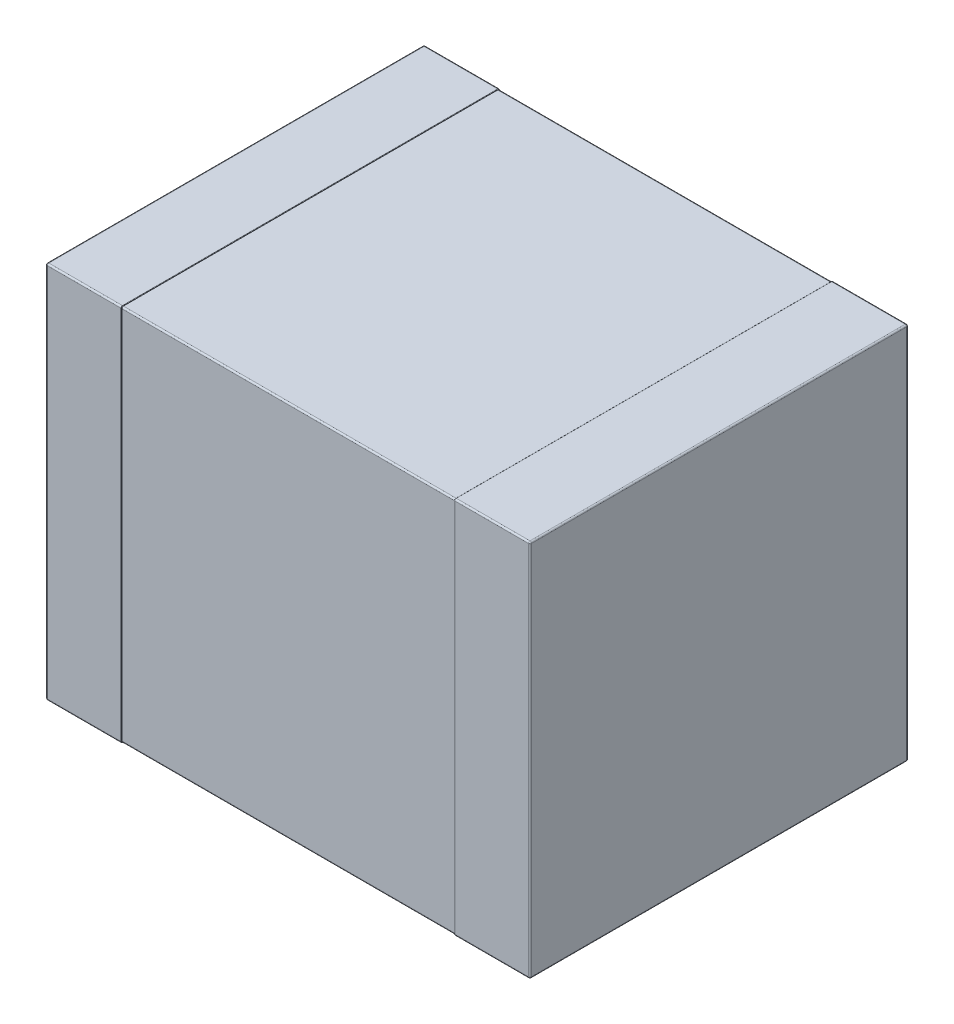
SolidWorks part; units mm, degrees
ref_plane "Top Plane" through (0, 0, 0) normal (0, 0, 1) x (1, 0, 0)
ref_plane "Front Plane" through (0, 0, 0) normal (0, 1, 0) x (1, 0, 0)
ref_plane "Side Plane" through (0, 0, 0) normal (1, 0, 0) x (0, 0, -1)
sketch "Sketch1" plane through (0, 0, 0) normal (0, 0, 1) x (1, 0, 0)
  line L1 (-1.6, 1.25) -> (1.6, 1.25)
  line L2 (-1.6, 1.25) -> (-1.6, -1.25)
  line L3 (-1.6, -1.25) -> (1.6, -1.25)
  line L4 (1.6, 1.25) -> (1.6, -1.25)
  dimension "D1" = 3.2
  dimension "D2" = 1.6
  dimension "D3" = 2.5
  dimension "D4" = 1.25
extrude "All body" add sketch "Sketch1" along normal blind 2.5
sketch "Sketch2" plane through (0, 0, 0) normal (1, 0, 0) x (0, 0, -1)
  line L14 (-0.003, 1.247) -> (-2.497, 1.247)
  line L15 (-0.003, -1.247) -> (-0.003, 1.247)
  line L16 (-2.497, -1.247) -> (-0.003, -1.247)
  line L17 (-2.497, 1.247) -> (-2.497, -1.247)
  line L18 (-0.003, 1.247) -> (-2.497, 1.247)
  line L19 (-0.003, -1.247) -> (-0.003, 1.247)
  line L20 (-2.497, -1.247) -> (-0.003, -1.247)
  line L21 (-2.497, 1.247) -> (-2.497, -1.247)
  dimension "D1" = 0.003
extrude "Cut out the body for pin" cut sketch "Sketch2" against normal blind 1.1 and the other way blind 1.1 flip side to cut
fillet "Body fillet" radius 0.01 4 edges at (0, 1.247, 0.003) (0, 1.247, 2.497) (0, -1.247, 0.003) (0, -1.247, 2.497)
fillet "Pin fillet a" radius 0.01 16 edges at (1.6, -1.25, 1.25) (1.6, 0, 2.5) (1.6, 1.25, 1.25) (1.6, 0, 0) (-1.6, 1.25, 1.25) (-1.6, 0, 2.5) (-1.6, -1.25, 1.25) (-1.6, 0, 0) (1.35, 1.25, 2.5) (1.35, -1.25, 2.5) (1.35, -1.25, 0) (1.35, 1.25, 0) (-1.35, 1.25, 0) (-1.35, -1.25, 0) (-1.35, 1.25, 2.5) (-1.35, -1.25, 2.5)
fillet "Pin fillet b" radius 0.003 16 edges at (1.1, -1.2471, 2.4971) (1.1, -1.25, 1.25) (1.1, -1.2471, 0.0029) (1.1, 0, 0) (1.1, 1.2471, 0.0029) (1.1, 1.25, 1.25) (1.1, 1.2471, 2.4971) (-1.1, -1.2471, 2.4971) (-1.1, -1.25, 1.25) (-1.1, -1.2471, 0.0029) (-1.1, 0, 0) (-1.1, 1.2471, 0.0029) (-1.1, 1.25, 1.25) (-1.1, 1.2471, 2.4971) (1.1, 0, 2.5) (-1.1, 0, 2.5)
